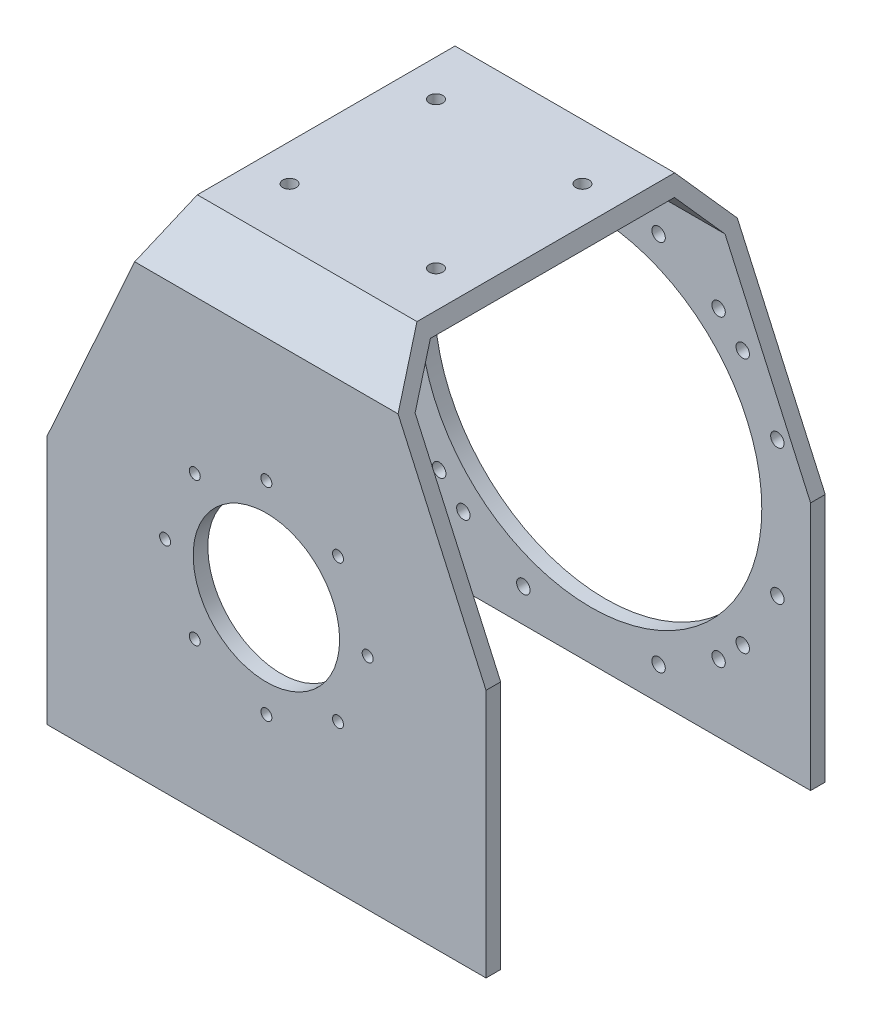
SolidWorks part; units mm, degrees
ref_plane "前视基准面" through (0, 0, 0) normal (0, 0, 1) x (1, 0, 0)
ref_plane "上视基准面" through (0, 0, 0) normal (0, 1, 0) x (1, 0, 0)
ref_plane "右视基准面" through (0, 0, 0) normal (1, 0, 0) x (0, 0, -1)
other "Configuration Table"
sketch "草图11" plane through (0, 0, 0) normal (1, 0, 0) x (0, 0, -1)
  line L0 (0, 0) -> (0, 82.4039) construction
  line L1 (-50, 196.0887) -> (50, 196.0887)
  line L2 (50, 196.0887) -> (63.5, 180)
  line L3 (63.5, 180) -> (63.5, 0)
  line L4 (-63.5, 180) -> (-63.5, 0)
  line L5 (-50, 196.0887) -> (-63.5, 180)
  point P10 (0, 196.0887)
  dimension "D1" = 63.5
  dimension "D2" = 180
  dimension "D3" = 100
  dimension "D4" = 40
extrude "拉伸-薄壁1" add sketch "草图11" along normal blind 180 thin thin type one direction wall 6
sketch "草图12" plane through (0, 0, 0) normal (0, 0, 1) x (1, 0, 0)
  line L0 (90, 283.6741) -> (90, -81.1896) construction
  line L1 (180, 182.1838) -> (180, 0) construction
  line L2 (0, 182.1838) -> (0, 0) construction
  line L3 (45, 202.0887) -> (0, 102.0887)
  line L4 (180, 202.0887) -> (0, 202.0887) construction
  line L5 (0, 102.0887) -> (0, 202.0887)
  line L6 (0, 202.0887) -> (0, 182.1838) construction
  line L7 (0, 202.0887) -> (45, 202.0887)
  line L8 (180, 102.0887) -> (180, 202.0887)
  line L9 (180, 202.0887) -> (135, 202.0887)
  line L10 (135, 202.0887) -> (180, 102.0887)
  circle A0 centre (90, 90) radius 85 construction
  dimension "D1" = 170
  dimension "D2" = 90
  dimension "D3" = 100
  dimension "D4" = 45
extrude "切除-拉伸1" cut sketch "草图12" against normal through all both and the other way through all
sketch "草图13" plane through (0, 0, -69.5) normal (0, 0, -1) x (-1, 0, 0)
  line L0 (-90, 90) -> (-90, 242.4141) construction
  line L1 (-90, 90) -> (-142.2916, 152.1864) construction
  line L2 (-90, 90) -> (-152.1864, 142.2916) construction
  line L3 (-90, 90) -> (-166.3791, 117.7092) construction
  line L4 (-117.7092, 166.3791) -> (-90, 90) construction
  circle A0 centre (-90, 90) radius 70
  circle A1 centre (-90, 90) radius 81.25 construction
  circle A2 centre (-117.7092, 166.3791) radius 2.75
  circle A3 centre (-142.2916, 152.1864) radius 2.75
  circle A4 centre (-152.1864, 142.2916) radius 2.75
  circle A5 centre (-166.3791, 117.7092) radius 2.75
  circle A6 centre (-13.6209, 117.7092) radius 2.75
  circle A7 centre (-27.8136, 142.2916) radius 2.75
  circle A8 centre (-37.7084, 152.1864) radius 2.75
  circle A9 centre (-62.2908, 166.3791) radius 2.75
  circle A10 centre (-62.2908, 13.6209) radius 2.75
  circle A11 centre (-37.7084, 27.8136) radius 2.75
  circle A12 centre (-27.8136, 37.7084) radius 2.75
  circle A13 centre (-13.6209, 62.2908) radius 2.75
  circle A14 centre (-166.3791, 62.2908) radius 2.75
  circle A15 centre (-152.1864, 37.7084) radius 2.75
  circle A16 centre (-142.2916, 27.8136) radius 2.75
  circle A17 centre (-117.7092, 13.6209) radius 2.75
  point P13 (-90, 90)
  point P40 (-90, 90)
  dimension "D1" = 140
  dimension "D2" = 162.5
  dimension "D3" = 5.5
  dimension "D4" = 30
  dimension "D5" = 30
  dimension "D6" = 9.88
  dimension "D7" = 4
extrude "切除-拉伸2" cut sketch "草图13" against normal blind 50
sketch "草图14" plane through (0, 202.0887, 0) normal (0, 1, 0) x (1, 0, 0)
  line L0 (0, 0) -> (194.3741, 0) construction
  line L1 (90, 89.7264) -> (90, -95.0261) construction
  line L2 (135, 52.7978) -> (135, -52.7978) construction
  line L3 (45, 52.7978) -> (45, -52.7978) construction
  circle A0 centre (120, 30) radius 2.75
  circle A1 centre (120, -30) radius 2.75
  circle A2 centre (60, -30) radius 2.75
  circle A3 centre (60, 30) radius 2.75
  dimension "D1" = 5.5
  dimension "D3" = 60
  dimension "D2" = 60
extrude "切除-拉伸3" cut sketch "草图14" against normal up to surface (6 mm away) up to face at (90, 196.0887, 0)
sketch "草图15" plane through (0, 0, 69.5) normal (0, 0, 1) x (1, 0, 0)
  line L0 (90, 272.4002) -> (90, -73.9333) construction
  line L1 (90, 283.6741) -> (90, -81.1896) construction
  circle A0 centre (90, 90) radius 30
  circle A1 centre (90, 90) radius 41.5 construction
  circle A2 centre (90, 131.5) radius 2.25
  circle A3 centre (119.3449, 119.3449) radius 2.25
  circle A4 centre (131.5, 90) radius 2.25
  circle A5 centre (119.3449, 60.6551) radius 2.25
  circle A6 centre (90, 48.5) radius 2.25
  circle A7 centre (60.6551, 60.6551) radius 2.25
  circle A8 centre (48.5, 90) radius 2.25
  circle A9 centre (60.6551, 119.3449) radius 2.25
  point P2 (90, 90)
  point P12 (120.8412, 57.0427)
  point P13 (90, 90)
  point P27 (90, 90)
  dimension "D1" = 60
  dimension "D2" = 83
  dimension "D3" = 4.5
  dimension "D4" = 8
extrude "切除-拉伸4" cut sketch "草图15" against normal up to surface (6 mm away) up to face at (90, 94.0296, 63.5)
